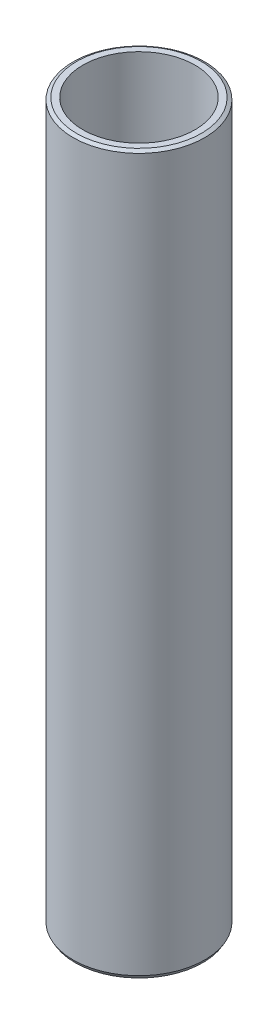
SolidWorks part; units mm, degrees
ref_plane "Front Plane" through (0, 0, 0) normal (0, 0, 1) x (1, 0, 0)
ref_plane "Top Plane" through (0, 0, 0) normal (0, 1, 0) x (1, 0, 0)
ref_plane "Right Plane" through (0, 0, 0) normal (1, 0, 0) x (0, 0, -1)
sketch "Sketch1" plane through (0, 0, 0) normal (0, 1, 0) x (1, 0, 0)
  circle A0 centre (0, 0) radius 55
  dimension "SHAFT_OD" = 110
extrude "Boss-Extrude1" add sketch "Sketch1" along normal blind 600
sketch "Sketch2" plane through (0, 0, 0) normal (0, 1, 0) x (1, 0, 0)
  circle A0 centre (0, 0) radius 46.8891
  dimension "BORE_D" = 93.7782
extrude "Cut-Extrude1" cut sketch "Sketch2" along normal through all
chamfer "Chamfer1" distance 1.6448 angle 60 2 edges at (0, 600, 55) (0, 0, 55) first distance on face at (0, 600, 55) first distance on face at (0, 0, 46.8891)
